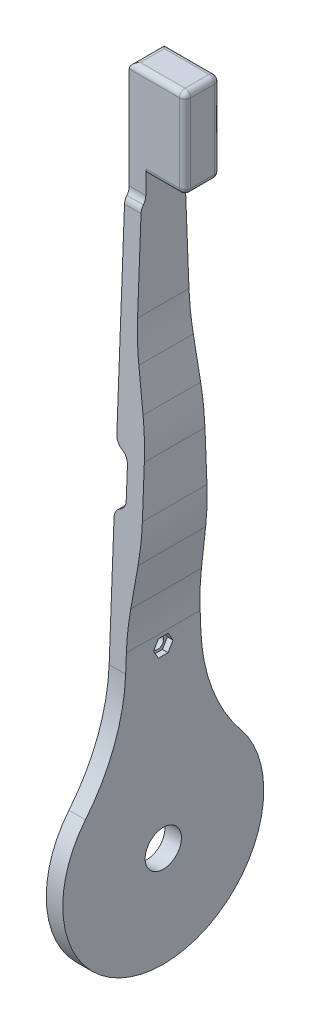
SolidWorks part; units mm, degrees
material "ABS"
ref_plane "Front Plane" through (0, 0, 0) normal (0, 0, 1) x (1, 0, 0)
ref_plane "Top Plane" through (0, 0, 0) normal (0, 1, 0) x (1, 0, 0)
ref_plane "Right Plane" through (0, 0, 0) normal (1, 0, 0) x (0, 0, -1)
sketch "Sketch2" plane through (0, 0, 0) normal (1, 0, 0) x (0, 0, -1)
  line L0 (4.9771, 193.675) -> (11.5599, 26.1323)
  line L1 (0, 193.675) -> (0, 28.575) construction
  line L2 (-4.9771, 193.675) -> (-11.5599, 26.1323)
  line L4 (-4.9771, 193.675) -> (4.9771, 193.675)
  circle A0 centre (0, 0) radius 28.575
  circle A1 centre (0, 0) radius 11.1125
  dimension "D1" = 57.15
  dimension "D5" = 22.225
  dimension "D2" = 11.5599
  dimension "D3" = 2.25
  dimension "D4" = 165.1
extrude "Boss-Extrude1" add sketch "Sketch2" against normal blind 6.35 contours A0 A1 region at (0, 15.1508, -23.269)
extrude "Boss-Extrude2" add sketch "Sketch2<5>" along normal blind 3.175 and the other way blind 1.524 contours L4 L1 A0 L0 | L1 L4 L2 A0 region at (0, 99.7845, -4.3525) region at (0, 99.7845, 4.3525)
sketch "Sketch2<5>" plane through (0, 0, 0) normal (1, 0, 0) x (0, 0, -1) same geometry as "Sketch2"
sketch "Sketch3" plane through (3.175, 0, 0) normal (1, 0, 0) x (0, 0, -1)
  line L0 (-4.9771, 193.675) -> (-4.9771, 168.275)
  line L1 (-4.9771, 168.275) -> (4.9771, 168.275)
  line L2 (4.9771, 168.275) -> (4.9771, 193.675)
  line L3 (-4.9771, 193.675) -> (4.9771, 193.675)
  dimension "D1" = 25.4
extrude "Boss-Extrude3" add sketch "Sketch3" along normal blind 11.176
sketch "Sketch4" plane through (3.175, 0, 0) normal (1, 0, 0) x (0, 0, -1)
  line L0 (-4.9771, 193.675) -> (-4.9771, 161.925)
  line L1 (-4.9771, 161.925) -> (-6.2246, 161.925)
  line L2 (-6.2246, 161.925) -> (-6.2246, 193.675)
  line L3 (-6.2246, 193.675) -> (-4.9771, 193.675)
  line L4 (-4.9771, 193.675) -> (-4.9086, 193.5806)
  line L5 (-4.9771, 193.675) -> (-11.5599, 26.1323) construction
  line L7 (0, 193.675) -> (0, 168.275) construction
  line L8 (-4.9771, 193.675) -> (4.9771, 193.675) construction
  line L9 (-4.9771, 168.275) -> (4.9771, 168.275) construction
  line L10 (4.9771, 193.675) -> (4.9086, 193.5806)
  line L11 (6.2246, 193.675) -> (4.9771, 193.675)
  line L12 (6.2246, 161.925) -> (6.2246, 193.675)
  line L13 (4.9771, 161.925) -> (6.2246, 161.925)
  line L14 (4.9771, 193.675) -> (4.9771, 161.925)
  line L15 (-4.9771, 168.275) -> (4.9771, 168.275) construction
  line M2 (4.9771, 193.675) -> (4.9771, 168.275)
  line M4 (-4.9771, 168.275) -> (-4.9771, 193.675)
  line M5 (-4.9771, 193.675) -> (-11.5599, 26.1323)
  line M7 (11.5599, 26.1323) -> (4.9771, 193.675)
  dimension "D1" = 6.35
extrude "Cut-Extrude1" cut sketch "Sketch4" against normal through all contours L1 M4 M5 | L13 M2 M7 region at (3.175, 172.5083, 5.3929) region at (3.175, 172.5083, -5.3929)
fillet "Fillet2" radius 3.175 2 edges at (0.8255, 161.925, 6.2246) (0.8255, 161.925, -6.2246)
fillet "Fillet4" radius 3.175 2 edges at (0.8255, 161.925, 4.9771) (0.8255, 161.925, -4.9771)
fillet "Fillet7" radius 1.5875 9 edges at (8.763, 168.275, 4.9771) (8.763, 168.275, -4.9771) (14.351, 180.975, -4.9771) (6.4135, 193.675, 4.9771) (14.351, 180.975, 4.9771) (-1.524, 193.675, 0) (14.351, 193.675, 0) (14.351, 168.275, 0) (6.4135, 193.675, -4.9771)
sketch "Sketch5" plane through (0, 0, 0) normal (1, 0, 0) x (0, 0, -1)
  circle A1 centre (0, 0) radius 28.575
  dimension "D1" = 57.15
extrude "Cut-Extrude2" cut sketch "Sketch5" against normal through all
sketch "Sketch6" plane through (3.175, 0, 0) normal (1, 0, 0) x (0, 0, -1)
  circle A0 centre (0, 0) radius 28.575
  arc A1 (11.5599, 26.1323) -> (-11.5599, 26.1323) centre (0, 0) ccw construction
extrude "Boss-Extrude4" add sketch "Sketch6" against normal up to surface (4.699 mm away) up to face at (-1.524, 140.683, 0)
hole_wizard "3/8 Clearance Hole1" positions "Sketch8" profile "Sketch7" hole size "3/8" standard "ANSI Inch" end condition through all
sketch "Sketch8" plane through (3.175, 0, 0) normal (1, 0, 0) x (0, 0, -1)
  point P0 (0, 0)
sketch "Sketch7" plane through (3.175, 0, 0) normal (0, 1, 0) x (0, 0, -1)
  line L0 (0, 0) -> (0, 4.699)
  line L1 (0, 4.699) -> (5.1587, 4.699)
  line L2 (5.1587, 4.699) -> (5.1587, 0)
  line L5 (5.1587, 0) -> (0, 0)
  line L11 (0, -6.35) -> (0, 107.95) construction
  dimension "Thru Hole Dia." = 10.3175
  dimension "Thru Hole Depth" = 4.699
fillet "Fillet9" radius 50.8 2 edges at (0.8255, 26.1323, 11.5599) (0.8255, 26.1323, -11.5599)
hole_wizard "#4 Clearance Hole1" positions "Sketch10" profile "Sketch9" hole size "#4" standard "ANSI Inch" end condition through all
sketch "Sketch10" plane through (3.175, 0, 0) normal (1, 0, 0) x (0, 0, -1)
  line L0 (-10.6266, 49.8873) -> (10.6266, 49.8873) construction
  line L1 (-6.3217, 159.4537) -> (-10.6911, 48.2456) construction
  line L2 (6.3217, 159.4537) -> (10.6911, 48.2456) construction
  line L5 (3.3896, 192.0875) -> (-3.3896, 192.0875) construction
  line L6 (65.0064, 32.4689) -> (0, 49.8873) construction
  line L7 (59.9587, -55.5099) -> (-83.6938, -17.0183) construction
  point P0 (0, 49.8873)
sketch "Sketch9" plane through (3.175, 49.8873, 0) normal (0, 1, 0) x (0, 0, -1)
  line L0 (0, 0) -> (0, 4.699)
  line L1 (0, 4.699) -> (1.7272, 4.699)
  line L2 (1.7272, 4.699) -> (1.7272, 0)
  line L5 (1.7272, 0) -> (0, 0)
  line L11 (0, -6.35) -> (0, 107.95) construction
  dimension "Thru Hole Dia." = 3.4544
  dimension "Thru Hole Depth" = 4.699
sketch "Sketch11" plane through (3.175, 0, 0) normal (1, 0, 0) x (0, 0, -1)
  line L0 (-1.3823, 47.493) -> (1.3823, 47.493)
  line L1 (-1.2357, 47.747) -> (1.2357, 47.747) construction
  line L2 (1.2357, 47.747) -> (2.4714, 49.8873) construction
  line L3 (2.4714, 49.8873) -> (1.2357, 52.0276) construction
  line L4 (1.2357, 52.0276) -> (-1.2357, 52.0276) construction
  line L5 (-1.2357, 52.0276) -> (-2.4714, 49.8873) construction
  line L6 (-2.4714, 49.8873) -> (-1.2357, 47.747) construction
  line L7 (1.3823, 47.493) -> (2.7647, 49.8873)
  line L8 (2.7647, 49.8873) -> (1.3823, 52.2816)
  line L9 (1.3823, 52.2816) -> (-1.3823, 52.2816)
  line L10 (-1.3823, 52.2816) -> (-2.7647, 49.8873)
  line L11 (-2.7647, 49.8873) -> (-1.3823, 47.493)
  line L12 (3.3896, 192.0875) -> (-3.3896, 192.0875) construction
  circle A0 centre (0, 49.8873) radius 2.1403 construction
  dimension "D1" = 0.254
extrude "Cut-Extrude3" cut sketch "Sketch11" against normal blind 1.6002
sketch "Sketch12" plane through (3.175, 0, 0) normal (1, 0, 0) x (0, 0, -1)
  line L0 (0.0633, -0.0824) -> (0.0633, 151.2674) construction
  circle A1 centre (0.0633, -0.0824) radius 93.8714 construction
  point P2 (0.0633, 93.7889)
sketch "Sketch13" plane through (3.175, 0, 0) normal (1, 0, 0) x (0, 0, -1)
  line L0 (6.3217, 159.4537) -> (10.6911, 48.2456) construction
  line L1 (-6.3217, 159.4537) -> (-10.6911, 48.2456) construction
  line L2 (8.4027, 106.4889) -> (9.4006, 81.0889)
  line L3 (-8.4027, 106.4889) -> (-9.4006, 81.0889)
  line L4 (-8.4027, 106.4889) -> (8.4027, 106.4889)
  line L5 (-9.4006, 81.0889) -> (9.4006, 81.0889)
  dimension "D1" = 12.7
  dimension "D2" = 25.4
extrude "Boss-Extrude5" add sketch "Sketch13" along normal offset from surface (3.2385 mm away) 7.9375 up to face at (-1.524, 49.8873, -1.7272)
sketch "Sketch14" plane through (0, 0, 0) normal (0, 0, 1) x (1, 0, 0)
  line L0 (-1.524, 101.7899) -> (1.7145, 100.1389)
  line L2 (1.7145, 100.1389) -> (1.7145, 87.4389)
  line L3 (1.7145, 93.7889) -> (3.175, 93.7889) construction
  line L4 (6.4135, 106.4889) -> (6.4135, 81.0889) construction
  line L5 (-1.524, 159.4537) -> (-1.524, 48.2456) construction
  line L7 (6.4135, 106.4889) -> (3.175, 106.4889) construction
  line L8 (-1.524, 101.7899) -> (-1.524, 85.7879)
  line L9 (-1.524, 85.7879) -> (1.7145, 87.4389)
  point P2 (0, 0)
  point P15 (-1.524, 93.7889)
  dimension "D1" = 4.699
  dimension "D2" = 4.699
  dimension "D3" = 6.35
extrude "Cut-Extrude4" cut sketch "Sketch14" against normal through all both and the other way through all
sketch "Sketch15" plane through (0, 0.4938, 12.5672) normal (0, 0.0393, 0.9992) x (1, 0, 0)
  line L0 (3.175, 80.6573) -> (3.175, 47.7887) construction
  line L1 (6.4135, 80.6573) -> (3.175, 80.6573) construction
  line L2 (6.4135, 106.0769) -> (3.175, 106.0769) construction
  line L3 (3.175, 159.0826) -> (3.175, 106.0769) construction
  line L4 (3.175, 80.6573) -> (3.175, 58.4323)
  line L5 (6.4135, 80.6573) -> (3.175, 80.6573)
  line L6 (6.4135, 106.0769) -> (3.175, 106.0769)
  line L7 (3.175, 128.3019) -> (3.175, 106.0769)
  line L8 (6.4135, 106.0769) -> (3.175, 128.3019)
  line L9 (6.4135, 80.6573) -> (3.175, 58.4323)
  dimension "D1" = 22.225
extrude "Boss-Extrude6" add sketch "Sketch15" along direction (0, 0, 1) on the side against the normal up to surface (20.5464 mm away) up to face at (1.905, 97.1425, -8.7699)
fillet "Fillet16" radius 3.175 2 edges at (1.7145, 100.1389, 0) (1.7145, 87.4389, 0)
fillet "Fillet17" radius 3.175 2 edges at (-1.524, 101.7899, 0) (-1.524, 85.7879, 0)
fillet "Fillet18" radius 76.2 4 edges at (3.175, 128.6968, 0) (6.4135, 106.4889, 0) (6.4135, 81.0889, 0) (3.175, 58.8811, 0)
